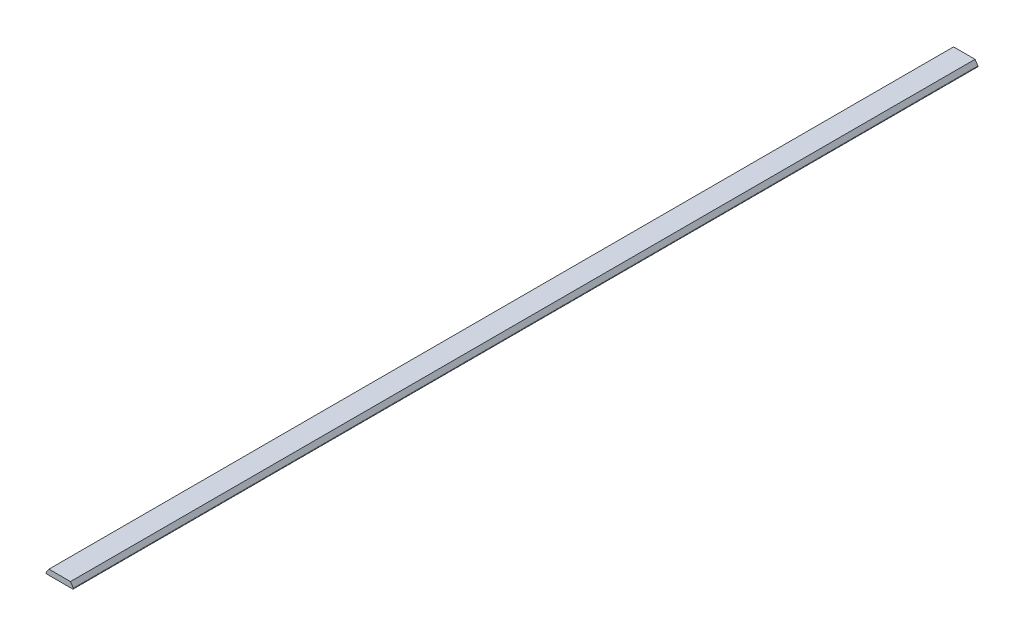
SolidWorks part; units mm, degrees
ref_plane "Front Plane" through (0, 0, 0) normal (0, 0, 1) x (1, 0, 0)
ref_plane "Top Plane" through (0, 0, 0) normal (0, 1, 0) x (1, 0, 0)
ref_plane "Right Plane" through (0, 0, 0) normal (1, 0, 0) x (0, 0, -1)
sketch "Sketch1" plane through (0, 0, 0) normal (0, 0, 1) x (1, 0, 0)
  line L1 (0, 5.5) -> (-2.8751, 1.1645)
  line L2 (-2.25, 0) -> (0, 0)
  line L3 (-3, 8.7252) -> (-3, 0.75) construction
  line L4 (0, 5.5) -> (22, 5.5)
  line L6 (22, 0) -> (0, 0)
  line L7 (11, 11.1244) -> (11, -4.8444) construction
  line L8 (24.25, 0) -> (22, 0)
  line L9 (22, 5.5) -> (24.8751, 1.1645)
  arc A0 (-2.25, 0) -> (-2.8751, 1.1645) centre (-2.25, 0.75) cw
  arc A1 (24.25, 0) -> (24.8751, 1.1645) centre (24.25, 0.75) ccw
  point P12 (11, 5.5)
  dimension "D2" = 0.75
  dimension "D1" = 5.5
  dimension "D4" = 56.45
  dimension "D5" = 22
  dimension "D3" = 3
extrude "Boss-Extrude1" add sketch "Sketch1" along normal blind 925
equation "\"WedgeHeight\"= 5.5mm'with tolerance"
equation "\"WedgeFillet\"= 0.75mm"
equation "\"WedgeExtend\"= 3mm"
equation "\"SlotWidth\"= 22mm"
equation "\"D1@Sketch1\"= \"WedgeHeight\""
equation "\"D2@Sketch1\"= \"WedgeFillet\""
equation "\"D3@Sketch1\"= \"WedgeExtend\""
equation "\"D5@Sketch1\"= \"SlotWidth\""
